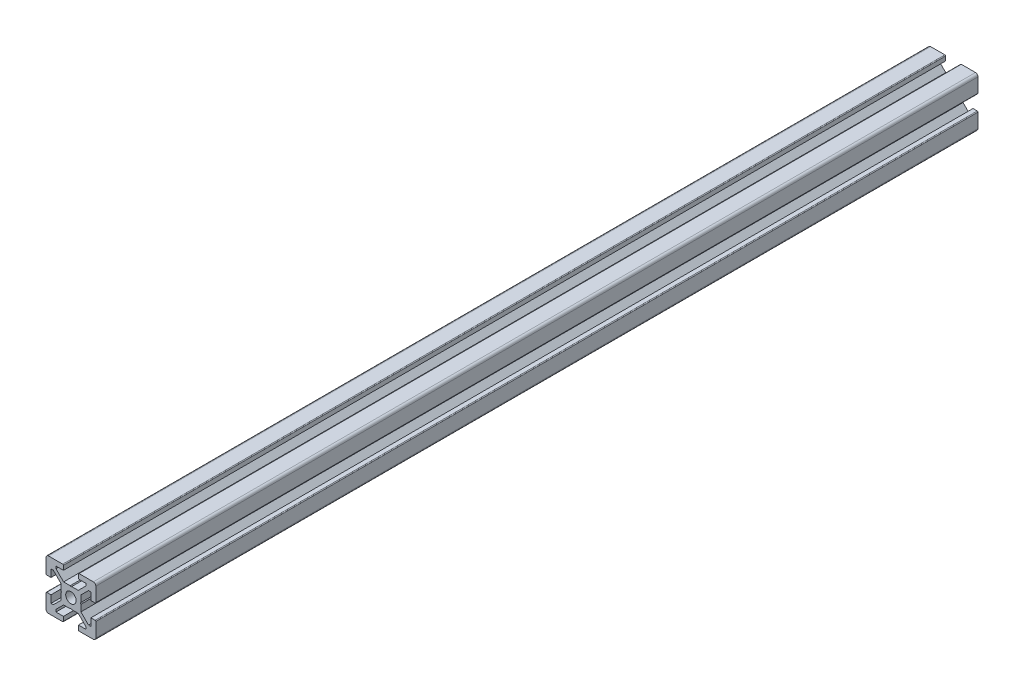
SolidWorks part; units mm, degrees
ref_plane "Front Plane" through (0, 0, 0) normal (0, 0, 1) x (1, 0, 0)
ref_plane "Top Plane" through (0, 0, 0) normal (0, 1, 0) x (1, 0, 0)
ref_plane "Right Plane" through (0, 0, 0) normal (1, 0, 0) x (0, 0, -1)
sketch "Sketch1" plane through (0, 0, 0) normal (0, 0, -1) x (-1, 0, 0)
  line L0 (10, 3.3) -> (10, 9)
  line L1 (9, 10) -> (3.3, 10)
  line L2 (3, 9.7) -> (3, 8)
  line L3 (3, 8) -> (6, 8)
  line L4 (6, 8) -> (6, 7.0607)
  line L5 (6, 7.0607) -> (2.9393, 4)
  line L6 (2.9393, 4) -> (0.3, 4)
  line L7 (0.3, 4) -> (0, 3.7)
  line L8 (0, 3.7) -> (-0.3, 4)
  line L9 (-0.3, 4) -> (-2.9393, 4)
  line L10 (-2.9393, 4) -> (-6, 7.0607)
  line L11 (-6, 7.0607) -> (-6, 8)
  line L12 (-6, 8) -> (-3, 8)
  line L13 (-3, 8) -> (-3, 9.7)
  line L14 (-3.3, 10) -> (-9, 10)
  line L15 (-10, 9) -> (-10, 3.3)
  line L16 (-9.7, 3) -> (-8, 3)
  line L17 (-8, 3) -> (-8, 6)
  line L18 (-8, 6) -> (-7.0607, 6)
  line L19 (-7.0607, 6) -> (-4, 2.9393)
  line L20 (-4, 2.9393) -> (-4, 0.3)
  line L21 (-4, 0.3) -> (-3.7, 0)
  line L22 (-3.7, 0) -> (-4, -0.3)
  line L23 (-4, -0.3) -> (-4, -2.9393)
  line L24 (-4, -2.9393) -> (-7.0607, -6)
  line L25 (-7.0607, -6) -> (-8, -6)
  line L26 (-8, -6) -> (-8, -3)
  line L27 (-8, -3) -> (-9.7, -3)
  line L28 (-10, -3.3) -> (-10, -9)
  line L29 (-9, -10) -> (-3.3, -10)
  line L30 (-3, -9.7) -> (-3, -8)
  line L31 (-3, -8) -> (-6, -8)
  line L32 (-6, -8) -> (-6, -7.0607)
  line L33 (-6, -7.0607) -> (-2.9393, -4)
  line L34 (-2.9393, -4) -> (-0.3, -4)
  line L35 (-0.3, -4) -> (0, -3.7)
  line L36 (0, -3.7) -> (0.3, -4)
  line L37 (0.3, -4) -> (2.9393, -4)
  line L38 (2.9393, -4) -> (6, -7.0607)
  line L39 (6, -7.0607) -> (6, -8)
  line L40 (6, -8) -> (3, -8)
  line L41 (3, -8) -> (3, -9.7)
  line L42 (3.3, -10) -> (9, -10)
  line L43 (10, -9) -> (10, -3.3)
  line L44 (9.7, -3) -> (8, -3)
  line L45 (8, -3) -> (8, -6)
  line L46 (8, -6) -> (7.0607, -6)
  line L47 (7.0607, -6) -> (4, -2.9393)
  line L48 (4, -2.9393) -> (4, -0.3)
  line L49 (4, -0.3) -> (3.7, 0)
  line L50 (3.7, 0) -> (4, 0.3)
  line L51 (4, 0.3) -> (4, 2.9393)
  line L52 (4, 2.9393) -> (7.0607, 6)
  line L53 (7.0607, 6) -> (8, 6)
  line L54 (8, 6) -> (8, 3)
  line L55 (8, 3) -> (9.7, 3)
  line L56 (9, -9) -> (-9, 9) construction
  line L57 (-9, -9) -> (9, 9) construction
  line L58 (-3.7, 0) -> (3.7, 0) construction
  line L59 (0, -3.7) -> (0, 3.7) construction
  circle A0 centre (0, 0) radius 2.1
  arc A1 (10, 9) -> (9, 10) centre (9, 9) ccw
  arc A2 (3.3, 10) -> (3, 9.7) centre (3.3, 9.7) ccw
  arc A3 (-3, 9.7) -> (-3.3, 10) centre (-3.3, 9.7) ccw
  arc A4 (-9, 10) -> (-10, 9) centre (-9, 9) ccw
  arc A5 (-10, 3.3) -> (-9.7, 3) centre (-9.7, 3.3) ccw
  arc A6 (-9.7, -3) -> (-10, -3.3) centre (-9.7, -3.3) ccw
  arc A7 (-10, -9) -> (-9, -10) centre (-9, -9) ccw
  arc A8 (-3.3, -10) -> (-3, -9.7) centre (-3.3, -9.7) ccw
  arc A9 (3, -9.7) -> (3.3, -10) centre (3.3, -9.7) ccw
  arc A10 (9, -10) -> (10, -9) centre (9, -9) ccw
  arc A11 (10, -3.3) -> (9.7, -3) centre (9.7, -3.3) ccw
  arc A12 (9.7, 3) -> (10, 3.3) centre (9.7, 3.3) ccw
  point P83 (0, 0)
  point P85 (0, 0)
  point P86 (0, 0)
  dimension "D1" = 1
  dimension "D4" = 0.3
  dimension "D10" = 4.2
  dimension "D2" = 20
  dimension "D3" = 6
  dimension "D5" = 3
  dimension "D6" = 1.7
  dimension "D7" = 0.9393
  dimension "D8" = 0.6
  dimension "D9" = 4
  dimension "D11" = 3.0607
  dimension "D12" = 3.0607
  dimension "D13" = 3.0607
  dimension "D14" = 5.7
  dimension "D15" = 5.7
  dimension "D16" = 0.9393
  dimension "D17" = 0.9393
  dimension "D18" = 3.0607
extrude "Boss-Extrude1" add sketch "Sketch1" against normal mid plane 354.05
ref_axis "Axis1" through (0, 0, 177.025) along (0, 0, -1)
